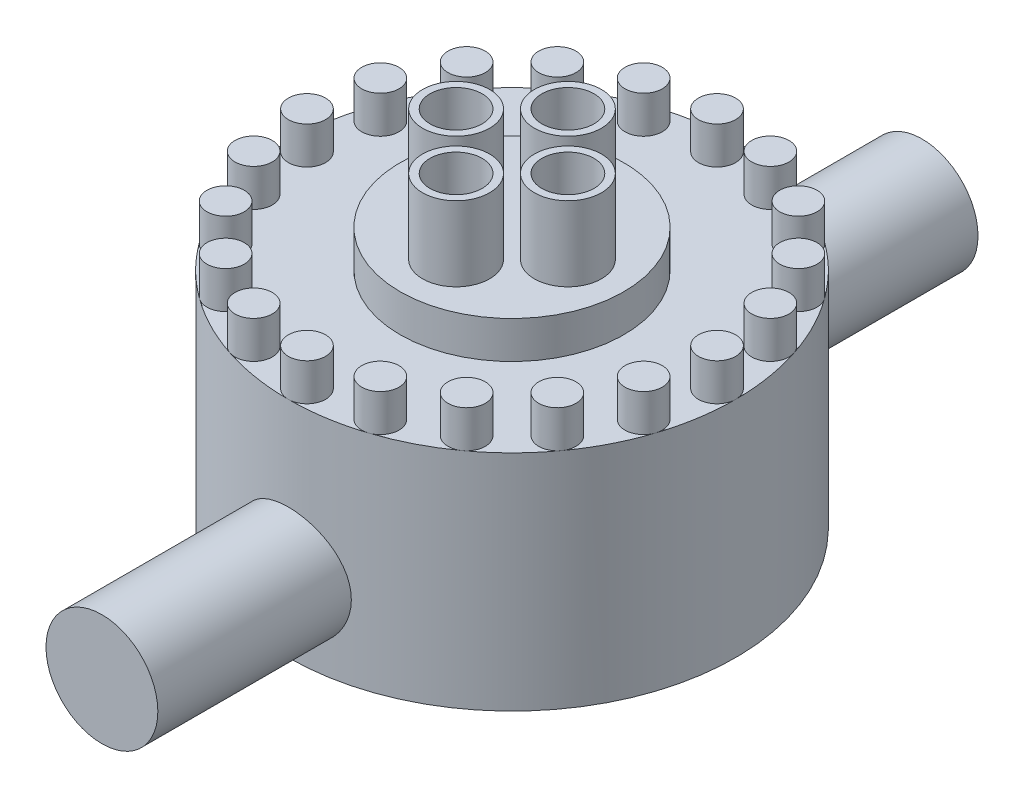
SolidWorks part; units mm, degrees
ref_plane "Front Plane" through (0, 0, 0) normal (0, 0, 1) x (1, 0, 0)
ref_plane "Top Plane" through (0, 0, 0) normal (0, 1, 0) x (1, 0, 0)
ref_plane "Right Plane" through (0, 0, 0) normal (1, 0, 0) x (0, 0, -1)
sketch "Sketch1" plane through (0, 0, 0) normal (0, 1, 0) x (1, 0, 0)
  circle A0 centre (0, 0) radius 300
  dimension "D1" = 600
extrude "Boss-Extrude1" add sketch "Sketch1" along normal blind 300
sketch "Sketch2" plane through (0, 300, 0) normal (0, 1, 0) x (1, 0, 0)
  line L0 (0, 0) -> (0, 275)
  circle A1 centre (0, 275) radius 25
  circle A2 centre (84.9797, 261.5405) radius 25
  circle A3 centre (161.6409, 222.4797) radius 25
  circle A4 centre (222.4797, 161.6409) radius 25
  circle A5 centre (261.5405, 84.9797) radius 25
  circle A6 centre (275, 0) radius 25
  circle A7 centre (261.5405, -84.9797) radius 25
  circle A8 centre (222.4797, -161.6409) radius 25
  circle A9 centre (161.6409, -222.4797) radius 25
  circle A10 centre (84.9797, -261.5405) radius 25
  circle A11 centre (0, -275) radius 25
  circle A12 centre (-84.9797, -261.5405) radius 25
  circle A13 centre (-161.6409, -222.4797) radius 25
  circle A14 centre (-222.4797, -161.6409) radius 25
  circle A15 centre (-261.5405, -84.9797) radius 25
  circle A16 centre (-275, 0) radius 25
  circle A17 centre (-261.5405, 84.9797) radius 25
  circle A18 centre (-222.4797, 161.6409) radius 25
  circle A19 centre (-161.6409, 222.4797) radius 25
  circle A20 centre (-84.9797, 261.5405) radius 25
  dimension "D2" = 20
  dimension "D1" = 275
extrude "Boss-Extrude2" add sketch "Sketch2" along normal blind 50 contours A20 | A19 | A18 | A17 | A16 | A15 | A14 | A13 | A12 | A11 | A10 | A9 | A8 | A7 | A6 | A5 | A4 | A3 | A2 | A1 region at (84.9797, 300, -261.5405) region at (161.6409, 300, -222.4797) region at (222.4797, 300, -161.6409) region at (261.5405, 300, -84.9797) region at (275, 300, 0) region at (261.5405, 300, 84.9797) region at (222.4797, 300, 161.6409) region at (161.6409, 300, 222.4797) region at (84.9797, 300, 261.5405) region at (0, 300, 275) region at (-84.9797, 300, 261.5405) region at (-161.6409, 300, 222.4797) region at (-222.4797, 300, 161.6409) region at (-261.5405, 300, 84.9797) region at (-275, 300, 0) region at (-261.5405, 300, -84.9797) region at (-222.4797, 300, -161.6409) region at (-161.6409, 300, -222.4797) region at (-84.9797, 300, -261.5405)
sketch "Sketch3" plane through (0, 300, 0) normal (0, 1, 0) x (1, 0, 0)
  circle A0 centre (0, 0) radius 125
  circle A1 centre (0, 0) radius 150
extrude "Boss-Extrude3" add sketch "Sketch3" along normal blind 50 contours A1
sketch "Sketch4" plane through (0, 350, 0) normal (0, 1, 0) x (1, 0, 0)
  line L0 (0, 0) -> (0, 75)
  circle A0 centre (0, 0) radius 75
  circle A1 centre (0, 75) radius 35
  circle A2 centre (75, 0) radius 35
  circle A3 centre (0, -75) radius 35
  circle A4 centre (-75, 0) radius 35
  dimension "D1" = 4
  dimension "D2" = 150
  dimension "D3" = 70
extrude "Cut-Extrude2" cut sketch "Sketch4" against normal through all contours A1 | A4 | A3 | A2
sketch "Sketch5" plane through (0, 350, 0) normal (0, 1, 0) x (1, 0, 0)
  circle A0 centre (0, 75) radius 45
  circle A1 centre (0, 75) radius 35
  circle A2 centre (75, 0) radius 45
  circle A3 centre (75, 0) radius 35
  circle A4 centre (0, -75) radius 45
  circle A5 centre (0, -75) radius 35
  circle A6 centre (-75, 0) radius 45
  circle A7 centre (-75, 0) radius 35
  dimension "D1" = 4
extrude "Boss-Extrude5" add sketch "Sketch5" along normal blind 100
ref_plane "Plane1" through (0, 0, 150) normal (0, 0, 1) x (1, 0, 0)
sketch "Sketch7" plane through (0, 0, 150) normal (0, 0, 1) x (1, 0, 0)
  line L0 (0, 0) -> (0, 100)
  circle A0 centre (0, 100) radius 75
  dimension "D1" = 100
extrude "Boss-Extrude6" add sketch "Sketch7" along normal blind 400 contours A0
ref_plane "Plane2" through (0, 0, -150) normal (0, 0, 1) x (1, 0, 0)
sketch "Sketch8" plane through (0, 0, -150) normal (0, 0, 1) x (1, 0, 0)
  line L0 (0, 0) -> (0, 102.5052)
  circle A0 centre (0, 102.5052) radius 75
extrude "Boss-Extrude7" add sketch "Sketch8" against normal blind 400 contours A0
